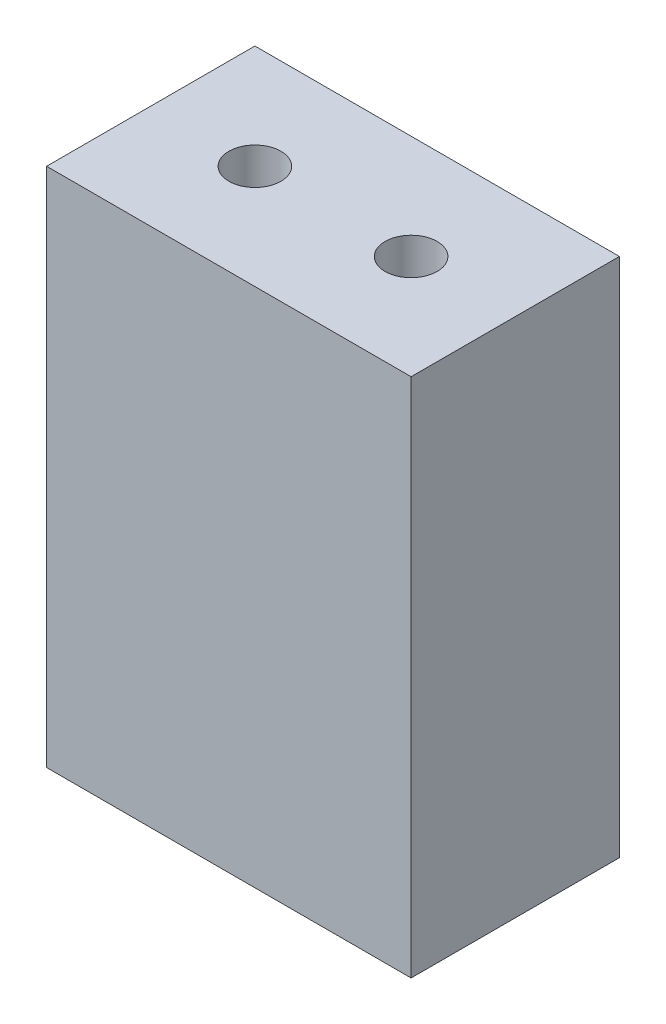
SolidWorks part; units mm, degrees
ref_plane "Front Plane" through (0, 0, 0) normal (0, 0, 1) x (1, 0, 0)
ref_plane "Top Plane" through (0, 0, 0) normal (0, 1, 0) x (1, 0, 0)
ref_plane "Right Plane" through (0, 0, 0) normal (1, 0, 0) x (0, 0, -1)
sketch "Sketch1" plane through (0, 0, 0) normal (0, 1, 0) x (1, 0, 0)
  line L1 (-17.5, 10) -> (17.5, 10)
  line L2 (-17.5, 10) -> (-17.5, -10)
  line L3 (-17.5, -10) -> (17.5, -10)
  line L4 (17.5, 10) -> (17.5, -10)
  point P4 (0, 10)
  point P6 (-17.5, 0)
  dimension "D1" = 35
  dimension "D2" = 20
extrude "Boss-Extrude1" add sketch "Sketch1" along normal blind 25 and the other way blind 25
sketch "Sketch2" plane through (0, 25, 0) normal (0, 1, 0) x (1, 0, 0)
  line L0 (0, 17.1762) -> (0, -20.8511) construction
  circle A1 centre (-7.5, 0) radius 2.5
  circle A2 centre (7.5, 0) radius 2.5
  point P0 (-7.1394, -0.3915)
  dimension "D1" = 5
  dimension "D2" = 15
extrude "Cut-Extrude1" cut sketch "Sketch2" against normal through all both and the other way through all
